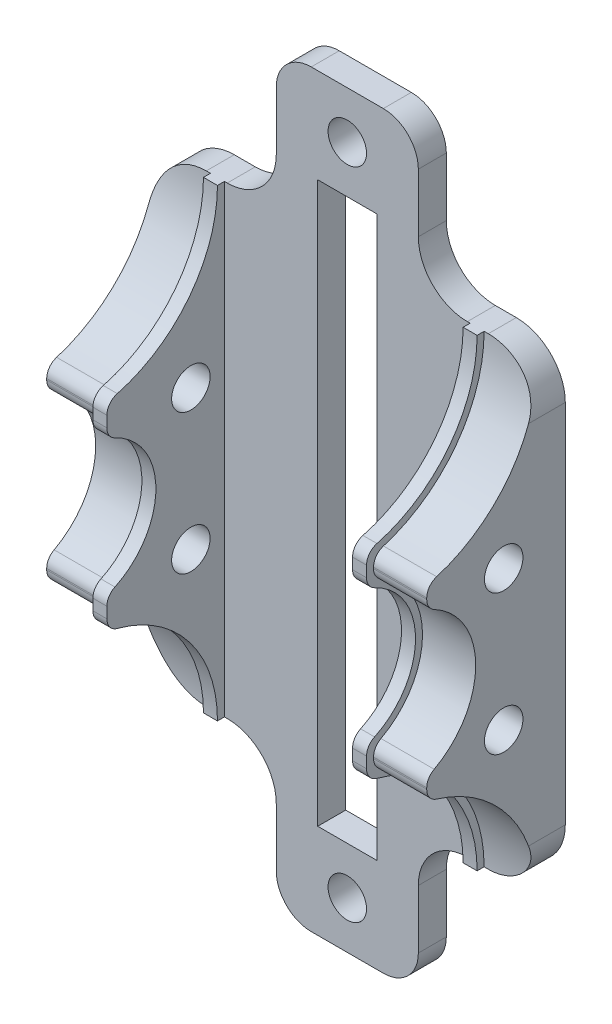
SolidWorks part; units mm, degrees
ref_plane "Front Plane" through (0, 0, 0) normal (0, 0, 1) x (1, 0, 0)
ref_plane "Top Plane" through (0, 0, 0) normal (0, 1, 0) x (1, 0, 0)
ref_plane "Right Plane" through (0, 0, 0) normal (1, 0, 0) x (0, 0, -1)
sketch "Sketch1" plane through (0, 0, 0) normal (0, 0, 1) x (1, 0, 0)
  line L20 (-62.15, 75) -> (-69.55, 75)
  line L21 (-69.55, 75) -> (-69.55, 65.75)
  line L22 (-69.55, 65.75) -> (-62.15, 65.75)
  line L23 (-62.15, 65.75) -> (-62.15, 64.25)
  line L24 (-62.15, 64.25) -> (-69.55, 64.25)
  line L25 (-69.55, 64.25) -> (-69.55, 55)
  line L26 (-69.55, 55) -> (-62.15, 55)
  line L27 (-62.15, 55) -> (-62.15, 11.5)
  line L28 (-62.15, 11.5) -> (-41.85, 11.5)
  line L29 (-41.85, 11.5) -> (-41.85, 55)
  line L30 (-41.85, 55) -> (-34.45, 55)
  line L31 (-34.45, 55) -> (-34.45, 64.25)
  line L32 (-34.45, 64.25) -> (-41.85, 64.25)
  line L33 (-41.85, 64.25) -> (-41.85, 65.75)
  line L34 (-41.85, 65.75) -> (-34.45, 65.75)
  line L35 (-34.45, 65.75) -> (-34.45, 75)
  line L36 (-34.45, 75) -> (-41.85, 75)
  line L37 (-41.85, 75) -> (-41.85, 118.5)
  line L38 (-41.85, 118.5) -> (-62.15, 118.5)
  line L39 (-62.15, 118.5) -> (-62.15, 75)
  line L40 (-62.15, 75) -> (-69.55, 75)
  line L41 (-69.55, 75) -> (-69.55, 65.75)
  line L42 (-69.55, 65.75) -> (-62.15, 65.75)
  line L43 (-62.15, 65.75) -> (-62.15, 64.25)
  line L44 (-62.15, 64.25) -> (-69.55, 64.25)
  line L45 (-69.55, 64.25) -> (-69.55, 55)
  line L46 (-69.55, 55) -> (-62.15, 55)
  line L47 (-62.15, 55) -> (-62.15, 11.5)
  line L48 (-62.15, 11.5) -> (-41.85, 11.5)
  line L49 (-41.85, 11.5) -> (-41.85, 55)
  line L50 (-41.85, 55) -> (-34.45, 55)
  line L51 (-34.45, 55) -> (-34.45, 64.25)
  line L52 (-34.45, 64.25) -> (-41.85, 64.25)
  line L53 (-41.85, 64.25) -> (-41.85, 65.75)
  line L54 (-41.85, 65.75) -> (-34.45, 65.75)
  line L55 (-34.45, 65.75) -> (-34.45, 75)
  line L56 (-34.45, 75) -> (-41.85, 75)
  line L57 (-41.85, 75) -> (-41.85, 118.5)
  line L58 (-41.85, 118.5) -> (-62.15, 118.5)
  line L59 (-62.15, 118.5) -> (-62.15, 75)
  circle A0 centre (-52, 111.75) radius 2.75 construction
  circle A1 centre (-52, 18.25) radius 2.75 construction
  circle A2 centre (-52, 111.75) radius 2.75
  circle A3 centre (-52, 18.25) radius 2.75
  dimension "D1" = 0
extrude "Boss-Extrude1" add sketch "Sketch1" along normal blind 4
fillet "Fillet1" radius 5 4 edges at (-62.15, 118.5, 2) (-41.85, 118.5, 2) (-62.15, 11.5, 2) (-41.85, 11.5, 2)
sketch "Sketch3" plane through (-34.45, 0, 0) normal (1, 0, 0) x (0, 0, -1)
  line L0 (-4, 65) -> (-4, 105)
  line L1 (-4, 64.25) -> (-4, 65.75) construction
  line L2 (-4, 65) -> (-24, 65)
  line L3 (-12.8, 65) -> (-19.8, 65)
  line L4 (-19.8, 65) -> (-19.8, 75.3827)
  line L5 (-19.8, 75.3827) -> (-19.8, 54.6173)
  line L6 (-19.8, 75.3827) -> (-19.8, 78.3827)
  line L7 (-19.8, 54.6173) -> (-19.8, 51.6173)
  line L8 (-4, 105) -> (-8.121, 105)
  line L9 (-19.8, 78.3827) -> (-19.8, 118.3827)
  line L10 (-19.8, 118.3827) -> (-49.8, 118.3827)
  line L11 (-4, 105) -> (-4, 26.6105)
  line L12 (-4, 16.5) -> (-4, 55) construction
  arc A0 (-19.8, 54.6173) -> (-19.8, 75.3827) centre (-24, 65) ccw
  arc A1 (-19.8, 78.3827) -> (-24.2472, 118.3827) centre (-24.2472, 98.1355) ccw
  circle A2 centre (-24.2472, 31.8645) radius 20.2472
  line M4 (-4, 75) -> (-4, 65.75)
  dimension "D3" = 22.4
  dimension "D1" = 40
  dimension "D2" = 20
  dimension "D4" = 7
  dimension "D5" = 3
  dimension "D6" = 3
  dimension "D7" = 40
  dimension "D8" = 30
extrude "Boss-Extrude3" add sketch "Sketch3" along normal blind 9.6 separate body contours A1 L6 A0 L2 L0 M4 | L7 A2 L11 L2 A0 region at (-34.45, 75.9842, 9.5197) region at (-34.45, 54.0158, 9.5197)
sketch "Sketch5" plane through (-34.45, 0, 0) normal (-1, 0, 0) x (0, 0, 1)
  line L3 (4, 98.1355) -> (4, 31.8645)
  line L4 (19.8, 51.6173) -> (19.8, 54.6173)
  line L5 (19.8, 75.3827) -> (19.8, 78.3827)
  line L6 (4, 98.1355) -> (4, 31.8645)
  line L7 (19.8, 51.6173) -> (19.8, 54.6173)
  line L8 (19.8, 75.3827) -> (19.8, 78.3827)
  arc A3 (4, 98.1355) -> (19.8, 78.3827) centre (24.2472, 98.1355) ccw
  arc A4 (19.8, 51.6173) -> (4, 31.8645) centre (24.2472, 31.8645) ccw
  arc A5 (19.8, 75.3827) -> (19.8, 54.6173) centre (24, 65) ccw
  arc A6 (4, 98.1355) -> (19.8, 78.3827) centre (24.2472, 98.1355) ccw
  arc A7 (19.8, 51.6173) -> (4, 31.8645) centre (24.2472, 31.8645) ccw
  arc A8 (19.8, 75.3827) -> (19.8, 54.6173) centre (24, 65) ccw
  dimension "D1" = 0
extrude "Boss-Extrude4" add sketch "Sketch5" along normal blind 10
sketch "Sketch6" plane through (0, 0, 4) normal (0, 0, -1) x (-1, 0, 0)
  line L12 (24.85, 31.8645) -> (41.85, 31.8645)
  line L13 (41.85, 31.8645) -> (41.85, 55)
  line L14 (41.85, 55) -> (34.45, 55)
  line L15 (34.45, 55) -> (34.45, 64.25)
  line L16 (34.45, 64.25) -> (41.85, 64.25)
  line L17 (41.85, 64.25) -> (41.85, 65.75)
  line L18 (41.85, 65.75) -> (34.45, 65.75)
  line L19 (34.45, 65.75) -> (34.45, 75)
  line L20 (34.45, 75) -> (41.85, 75)
  line L21 (41.85, 75) -> (41.85, 98.1355)
  line L22 (41.85, 98.1355) -> (24.85, 98.1355)
  line L23 (24.85, 98.1355) -> (24.85, 31.8645)
  line L24 (24.85, 31.8645) -> (41.85, 31.8645)
  line L25 (41.85, 31.8645) -> (41.85, 55)
  line L26 (41.85, 55) -> (34.45, 55)
  line L27 (34.45, 55) -> (34.45, 64.25)
  line L28 (34.45, 64.25) -> (41.85, 64.25)
  line L29 (41.85, 64.25) -> (41.85, 65.75)
  line L30 (41.85, 65.75) -> (34.45, 65.75)
  line L31 (34.45, 65.75) -> (34.45, 75)
  line L32 (34.45, 75) -> (41.85, 75)
  line L33 (41.85, 75) -> (41.85, 98.1355)
  line L34 (41.85, 98.1355) -> (24.85, 98.1355)
  line L35 (24.85, 98.1355) -> (24.85, 31.8645)
  dimension "D1" = 0
extrude "Boss-Extrude5" add sketch "Sketch6" along normal up to surface (4 mm away) up to face at (-49.25, 111.75, 0)
sketch "Sketch7" plane through (0, 0, 19.8) normal (0, 0, 1) x (1, 0, 0)
  line L0 (-31.85, 76) -> (-31.85, 98.1355)
  line L1 (-41.85, 98.1355) -> (-24.85, 98.1355) construction
  line L2 (-31.85, 98.1355) -> (-32.45, 98.1355)
  line L3 (-32.45, 98.1355) -> (-32.45, 31.8645)
  line L4 (-41.85, 31.8645) -> (-24.85, 31.8645) construction
  line L5 (-32.45, 31.8645) -> (-31.85, 31.8645)
  dimension "D1" = 0.6
  dimension "D2" = 0.6
sketch "Sketch9" plane through (-44.45, 0, 0) normal (-1, 0, 0) x (0, 0, 1)
  line L17 (5, 31.8645) -> (4, 31.8645)
  line L18 (4, 55) -> (4, 16.5) construction
  line L19 (20.8, 79.1995) -> (20.8, 74.685)
  line L20 (20.8, 55.315) -> (20.8, 50.8005)
  line L21 (20.8, 79.1995) -> (20.8, 74.685)
  line L22 (20.8, 55.315) -> (20.8, 50.8005)
  line L23 (5, 98.1355) -> (4, 98.1355)
  line L24 (4, 98.1355) -> (4, 31.8645)
  line L25 (19.8, 75.3827) -> (19.8, 78.3827) construction
  line L26 (19.8, 51.6173) -> (19.8, 54.6173) construction
  line L27 (19.8, 75.3827) -> (19.8, 78.3827)
  line L28 (19.8, 51.6173) -> (19.8, 54.6173)
  arc A11 (20.175, 74.4557) -> (20.175, 55.5443) centre (24, 65) ccw
  arc A12 (20.175, 74.4557) -> (20.175, 55.5443) centre (24, 65) ccw
  arc A19 (4, 98.1355) -> (19.8, 78.3827) centre (24.2472, 98.1355) ccw construction
  arc A20 (19.8, 75.3827) -> (19.8, 54.6173) centre (24, 65) ccw construction
  arc A21 (19.8, 51.6173) -> (4, 31.8645) centre (24.2472, 31.8645) ccw construction
  arc A22 (20.8, 74.685) -> (20.8, 55.315) centre (24, 65) ccw
  arc A23 (5, 98.1355) -> (20.8, 79.1995) centre (24.2472, 98.1355) ccw
  arc A24 (20.8, 50.8005) -> (5, 31.8645) centre (24.2472, 31.8645) ccw
  arc A25 (20.8, 74.685) -> (20.8, 55.315) centre (24, 65) ccw
  arc A26 (5, 98.1355) -> (20.8, 79.1995) centre (24.2472, 98.1355) ccw
  arc A27 (20.8, 50.8005) -> (5, 31.8645) centre (24.2472, 31.8645) ccw
  arc A28 (4, 98.1355) -> (19.8, 78.3827) centre (24.2472, 98.1355) ccw
  arc A29 (19.8, 75.3827) -> (19.8, 54.6173) centre (24, 65) ccw
  arc A30 (19.8, 51.6173) -> (4, 31.8645) centre (24.2472, 31.8645) ccw
  arc M7 (19.8, 78.3827) -> (4, 98.1355) centre (24.2472, 98.1355) cw
  arc M9 (4, 31.8645) -> (19.8, 51.6173) centre (24.2472, 31.8645) cw
  line M10 (19.8, 51.6173) -> (19.8, 54.6173)
  arc M11 (19.8, 54.6173) -> (19.8, 75.3827) centre (24, 65) cw
  line M12 (19.8, 75.3827) -> (19.8, 78.3827)
  dimension "D1" = 1
  dimension "D2" = 1
extrude "Boss-Extrude6" add sketch "Sketch9" against normal blind 12 contours A27 L22 A25 A12 L21 A26 L23 L17 M7 M12 M11 M10 M9 region at (-44.45, 32.5482, 4.5)
sketch "Sketch10" plane through (-44.45, 0, 0) normal (-1, 0, 0) x (0, 0, 1)
  line L5 (4, 98.1355) -> (4, 31.8645)
  line L6 (4, 31.8645) -> (5, 31.8645)
  line L7 (20.8, 50.8005) -> (20.8, 55.315)
  line L8 (20.8, 74.685) -> (20.8, 79.1995)
  line L9 (5, 98.1355) -> (4, 98.1355)
  line L10 (4, 98.1355) -> (4, 31.8645)
  line L11 (4, 31.8645) -> (5, 31.8645)
  line L12 (20.8, 50.8005) -> (20.8, 55.315)
  line L13 (20.8, 74.685) -> (20.8, 79.1995)
  line L14 (5, 98.1355) -> (4, 98.1355)
  arc A3 (20.8, 50.8005) -> (5, 31.8645) centre (24.2472, 31.8645) ccw
  arc A4 (20.8, 74.685) -> (20.8, 55.315) centre (24, 65) ccw
  arc A5 (5, 98.1355) -> (20.8, 79.1995) centre (24.2472, 98.1355) ccw
  arc A6 (20.8, 50.8005) -> (5, 31.8645) centre (24.2472, 31.8645) ccw
  arc A7 (20.8, 74.685) -> (20.8, 55.315) centre (24, 65) ccw
  arc A8 (5, 98.1355) -> (20.8, 79.1995) centre (24.2472, 98.1355) ccw
  dimension "D1" = 0
extrude "Cut-Extrude1" cut sketch "Sketch10" against normal blind 10
sketch "Sketch12" plane through (0, 0, 4) normal (0, 0, 1) x (1, 0, 0)
  line L0 (-41.85, 31.8645) -> (-62.15, 31.8645)
  line L1 (-62.15, 55) -> (-62.15, 16.5) construction
  line L2 (-62.15, 31.8645) -> (-79.15, 31.8645)
  line L3 (-32.45, 98.1355) -> (-62.15, 98.1355)
  line L4 (-62.15, 113.5) -> (-62.15, 75) construction
  line L5 (-62.15, 98.1355) -> (-79.15, 98.1355)
  line L6 (-79.15, 31.8645) -> (-79.15, 98.1355)
  line L7 (-62.15, 98.1355) -> (-62.15, 31.8645)
  line M11 (-62.15, 113.5) -> (-62.15, 75)
  line M12 (-62.15, 75) -> (-69.55, 75)
  line M13 (-69.55, 75) -> (-69.55, 65.75)
  line M14 (-69.55, 65.75) -> (-62.15, 65.75)
  line M15 (-62.15, 65.75) -> (-62.15, 64.25)
  line M16 (-62.15, 64.25) -> (-69.55, 64.25)
  line M17 (-69.55, 64.25) -> (-69.55, 55)
  line M18 (-69.55, 55) -> (-62.15, 55)
  line M19 (-62.15, 55) -> (-62.15, 16.5)
  dimension "D1" = 17
  dimension "D2" = 17
extrude "Boss-Extrude7" add sketch "Sketch12" against normal up to surface (4 mm away) contours L6 L2 L5 M19 M18 M17 M16 M15 M14 M13 M12 M11 region at (-71.314, 65, 4) up to face at (-49.25, 111.75, 0)
sketch "Sketch13" plane through (-79.15, 0, 0) normal (-1, 0, 0) x (0, 0, 1)
  line L5 (19.8, 75.3827) -> (19.8, 78.3827)
  line L6 (19.8, 51.6173) -> (19.8, 54.6173)
  line L7 (0, 31.8645) -> (4, 31.8645)
  line L8 (0, 98.1355) -> (0, 31.8645)
  line L9 (4, 98.1355) -> (0, 98.1355)
  line L10 (19.8, 75.3827) -> (19.8, 78.3827)
  line L11 (19.8, 51.6173) -> (19.8, 54.6173)
  line L12 (0, 31.8645) -> (4, 31.8645)
  line L13 (0, 98.1355) -> (0, 31.8645)
  line L14 (4, 98.1355) -> (0, 98.1355)
  arc A3 (4, 98.1355) -> (19.8, 78.3827) centre (24.2472, 98.1355) ccw
  arc A4 (19.8, 75.3827) -> (19.8, 54.6173) centre (24, 65) ccw
  arc A5 (19.8, 51.6173) -> (4, 31.8645) centre (24.2472, 31.8645) ccw
  arc A6 (4, 98.1355) -> (19.8, 78.3827) centre (24.2472, 98.1355) ccw
  arc A7 (19.8, 75.3827) -> (19.8, 54.6173) centre (24, 65) ccw
  arc A8 (19.8, 51.6173) -> (4, 31.8645) centre (24.2472, 31.8645) ccw
  dimension "D1" = 0
extrude "Boss-Extrude8" add sketch "Sketch13" against normal blind 7.6
sketch "Sketch14" plane through (-71.55, 0, 0) normal (1, 0, 0) x (0, 0, -1)
  line L5 (-4, 98.1355) -> (-5, 98.1355)
  line L6 (-4, 31.8645) -> (-4, 98.1355)
  line L7 (-5, 31.8645) -> (-4, 31.8645)
  line L8 (-20.8, 55.315) -> (-20.8, 50.8005)
  line L9 (-20.8, 79.1995) -> (-20.8, 74.685)
  line L10 (-4, 98.1355) -> (-5, 98.1355)
  line L11 (-4, 31.8645) -> (-4, 98.1355)
  line L12 (-5, 31.8645) -> (-4, 31.8645)
  line L13 (-20.8, 55.315) -> (-20.8, 50.8005)
  line L14 (-20.8, 79.1995) -> (-20.8, 74.685)
  arc A3 (-5, 31.8645) -> (-20.8, 50.8005) centre (-24.2472, 31.8645) ccw
  arc A4 (-20.8, 55.315) -> (-20.8, 74.685) centre (-24, 65) ccw
  arc A5 (-20.8, 79.1995) -> (-5, 98.1355) centre (-24.2472, 98.1355) ccw
  arc A6 (-5, 31.8645) -> (-20.8, 50.8005) centre (-24.2472, 31.8645) ccw
  arc A7 (-20.8, 55.315) -> (-20.8, 74.685) centre (-24, 65) ccw
  arc A8 (-20.8, 79.1995) -> (-5, 98.1355) centre (-24.2472, 98.1355) ccw
  dimension "D1" = 0
extrude "Boss-Extrude9" add sketch "Sketch14" along normal blind 2
fillet "Fillet2" radius 7 8 edges at (-79.15, 98.1355, 2) (-62.15, 98.1355, 2) (-41.85, 98.1355, 2) (-24.85, 98.1355, 2) (-24.85, 31.8645, 2) (-79.15, 31.8645, 2) (-62.15, 31.8645, 2) (-41.85, 31.8645, 2)
sketch "Sketch15" plane through (0, 0, 0) normal (0, 0, -1) x (-1, 0, 0)
  line L1 (47.775, 25) -> (56.225, 25)
  line L2 (47.775, 25) -> (47.775, 105)
  line L3 (47.775, 105) -> (56.225, 105)
  line L4 (56.225, 25) -> (56.225, 105)
extrude "Cut-Extrude2" cut sketch "Sketch15" against normal blind 14
fillet "Fillet3" radius 2 16 edges at (-70.55, 79.1995, 20.8) (-70.55, 74.685, 20.8) (-33.45, 79.1995, 20.8) (-28.65, 75.3827, 19.8) (-28.65, 78.3827, 19.8) (-33.45, 74.685, 20.8) (-33.45, 50.8005, 20.8) (-33.45, 55.315, 20.8) (-28.65, 54.6173, 19.8) (-28.65, 51.6173, 19.8) (-75.35, 78.3827, 19.8) (-75.35, 75.3827, 19.8) (-75.35, 54.6173, 19.8) (-75.35, 51.6173, 19.8) (-70.55, 55.315, 20.8) (-70.55, 50.8005, 20.8)
sketch "Sketch17" plane through (-24.85, 0, 0) normal (1, 0, 0) x (0, 0, -1)
  line L0 (-12.8, 65) -> (-4.8, 65)
  line L2 (-8.8, 65) -> (-8.8, 75)
  arc A0 (-18.7394, 55.1123) -> (-18.7394, 74.8877) centre (-24, 65) ccw construction
  circle A1 centre (-8.8, 75) radius 2.75
  circle A2 centre (-8.8, 55) radius 2.75
  dimension "D2" = 5.5
  dimension "D1" = 10
  dimension "D3" = 8
extrude "Cut-Extrude4" cut sketch "Sketch17" against normal through all both and the other way through all contours A1 | A2 region at (-24.85, 73.1105, 6.9105)
